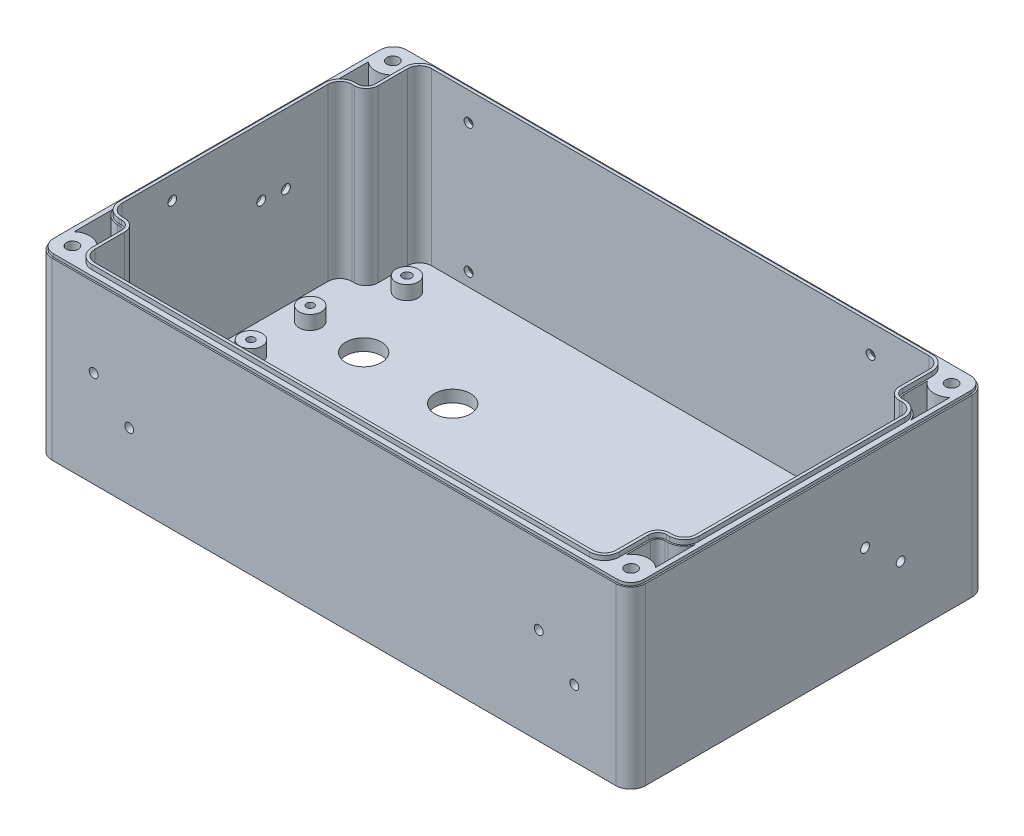
SolidWorks part; units mm, degrees
ref_plane "Front Plane" through (0, 0, 0) normal (0, 0, 1) x (1, 0, 0)
ref_plane "Top Plane" through (0, 0, 0) normal (0, 1, 0) x (1, 0, 0)
ref_plane "Right Plane" through (0, 0, 0) normal (1, 0, 0) x (0, 0, -1)
sketch "Sketch1" plane through (0, 0, 0) normal (0, 1, 0) x (1, 0, 0)
  line L1 (-100, 60) -> (100, 60)
  line L2 (-100, 60) -> (-100, -60)
  line L3 (-100, -60) -> (100, -60)
  line L4 (100, 60) -> (100, -60)
  line L5 (-100, 60) -> (100, -60) construction
  line L6 (-100, -60) -> (100, 60) construction
  point P0 (0, 0)
  dimension "D1" = 200
  dimension "D2" = 120
extrude "Boss-Extrude1" add sketch "Sketch1" along normal blind 60
fillet "Fillet1" radius 5 4 edges at (-100, 30, -60) (100, 30, -60) (100, 30, 60) (-100, 30, 60)
sketch "Sketch2" plane through (0, 60, 0) normal (0, 1, 0) x (1, 0, 0)
  line L0 (0, 60) -> (0, -60) construction
  line L1 (96.7, 56.7) -> (-96.7, 56.7)
  line L2 (96.7, 56.7) -> (96.7, -56.7)
  line L3 (96.7, -56.7) -> (-96.7, -56.7)
  line L4 (-96.7, 56.7) -> (-96.7, -56.7)
  line L5 (96.7, 56.7) -> (-96.7, -56.7) construction
  line L6 (96.7, -56.7) -> (-96.7, 56.7) construction
  line L7 (95, 60) -> (-95, 60) construction
  line L8 (-95, -60) -> (95, -60) construction
  line L9 (-100, 0) -> (99.9439, 0) construction
  line L10 (-100, 55) -> (-100, -55) construction
  line L12 (87.85, -56.7) -> (-87.85, -56.7)
  line L13 (87.85, -56.7) -> (87.85, 56.7)
  line L14 (87.85, 56.7) -> (-87.85, 56.7)
  line L15 (-87.85, -56.7) -> (-87.85, 56.7)
  line L16 (87.85, -56.7) -> (-87.85, 56.7) construction
  line L17 (87.85, 56.7) -> (-87.85, -56.7) construction
  line L18 (96.7, -38.7) -> (-96.7, -38.7)
  line L19 (96.7, -38.7) -> (96.7, 38.7)
  line L20 (96.7, 38.7) -> (-96.7, 38.7)
  line L21 (-96.7, -38.7) -> (-96.7, 38.7)
  line L22 (96.7, -38.7) -> (-96.7, 38.7) construction
  line L23 (96.7, 38.7) -> (-96.7, -38.7) construction
  circle A0 centre (-94.15, 54) radius 2
  circle A2 centre (94.15, 54) radius 2
  circle A3 centre (94.15, -54) radius 2
  circle A4 centre (-94.15, -54) radius 2
  point P0 (0, 0)
  point P18 (0, 0)
  point P19 (0, 0)
  dimension "D5" = 4
  dimension "D1" = 193.4
  dimension "D2" = 113.4
  dimension "D3" = 188.3
  dimension "D4" = 108
  dimension "D6" = 175.7
  dimension "D7" = 77.4
extrude "Cut-Extrude1" cut sketch "Sketch2" against normal offset from surface (56 mm away) 4 contours L20 L13 L1 L15 | L13 L20 L15 L18 | L13 L18 L15 L3 | L15 L20 L4 L18 | L2 L20 L13 L18 | A0 | A4 | A2 | A3 region at (0, 60, -47.7) region at (92.275, 60, 0) region at (0, 60, 0) region at (-92.275, 60, 0) region at (0, 60, 47.7) up to face at (0, 0, 0)
fillet "Fillet2" radius 4 12 edges at (87.85, 32, -56.7) (87.85, 32, -38.7) (96.7, 32, -38.7) (96.7, 32, 38.7) (87.85, 32, 38.7) (87.85, 32, 56.7) (-87.85, 32, 56.7) (-87.85, 32, 38.7) (-96.7, 32, 38.7) (-96.7, 32, -38.7) (-87.85, 32, -56.7) (-87.85, 32, -38.7)
sketch "Sketch3" plane through (0, 60, 0) normal (0, 1, 0) x (1, 0, 0)
  line L1 (83.85, 57.7) -> (-83.85, 57.7)
  line L2 (-88.85, 52.7) -> (-88.85, 42.7)
  line L3 (-91.85, 39.7) -> (-92.7, 39.7)
  line L4 (-97.7, 34.7) -> (-97.7, -34.7)
  line L5 (-92.7, -39.7) -> (-91.85, -39.7)
  line L6 (-88.85, -42.7) -> (-88.85, -52.7)
  line L7 (-83.85, -57.7) -> (83.85, -57.7)
  line L8 (88.85, -52.7) -> (88.85, -42.7)
  line L9 (91.85, -39.7) -> (92.7, -39.7)
  line L10 (97.7, -34.7) -> (97.7, 34.7)
  line L11 (92.7, 39.7) -> (91.85, 39.7)
  line L12 (88.85, 42.7) -> (88.85, 52.7)
  line L13 (87.85, 42.7) -> (87.85, 52.7)
  line L14 (92.7, 38.7) -> (91.85, 38.7)
  line L15 (96.7, -34.7) -> (96.7, 34.7)
  line L16 (91.85, -38.7) -> (92.7, -38.7)
  line L17 (87.85, -52.7) -> (87.85, -42.7)
  line L18 (-83.85, -56.7) -> (83.85, -56.7)
  line L19 (-87.85, -42.7) -> (-87.85, -52.7)
  line L20 (-92.7, -38.7) -> (-91.85, -38.7)
  line L21 (-96.7, 34.7) -> (-96.7, -34.7)
  line L22 (-91.85, 38.7) -> (-92.7, 38.7)
  line L23 (-87.85, 52.7) -> (-87.85, 42.7)
  line L24 (83.85, 56.7) -> (-83.85, 56.7)
  line L25 (87.85, 42.7) -> (87.85, 52.7)
  line L26 (92.7, 38.7) -> (91.85, 38.7)
  line L27 (96.7, -34.7) -> (96.7, 34.7)
  line L28 (91.85, -38.7) -> (92.7, -38.7)
  line L29 (87.85, -52.7) -> (87.85, -42.7)
  line L30 (-83.85, -56.7) -> (83.85, -56.7)
  line L31 (-87.85, -42.7) -> (-87.85, -52.7)
  line L32 (-92.7, -38.7) -> (-91.85, -38.7)
  line L33 (-96.7, 34.7) -> (-96.7, -34.7)
  line L34 (-91.85, 38.7) -> (-92.7, 38.7)
  line L35 (-87.85, 52.7) -> (-87.85, 42.7)
  line L36 (83.85, 56.7) -> (-83.85, 56.7)
  arc A0 (-83.85, 57.7) -> (-88.85, 52.7) centre (-83.85, 52.7) ccw
  arc A1 (-91.85, 39.7) -> (-88.85, 42.7) centre (-91.85, 42.7) ccw
  arc A2 (-92.7, 39.7) -> (-97.7, 34.7) centre (-92.7, 34.7) ccw
  arc A3 (-97.7, -34.7) -> (-92.7, -39.7) centre (-92.7, -34.7) ccw
  arc A4 (-88.85, -42.7) -> (-91.85, -39.7) centre (-91.85, -42.7) ccw
  arc A5 (-88.85, -52.7) -> (-83.85, -57.7) centre (-83.85, -52.7) ccw
  arc A6 (83.85, -57.7) -> (88.85, -52.7) centre (83.85, -52.7) ccw
  arc A7 (91.85, -39.7) -> (88.85, -42.7) centre (91.85, -42.7) ccw
  arc A8 (92.7, -39.7) -> (97.7, -34.7) centre (92.7, -34.7) ccw
  arc A9 (97.7, 34.7) -> (92.7, 39.7) centre (92.7, 34.7) ccw
  arc A10 (88.85, 42.7) -> (91.85, 39.7) centre (91.85, 42.7) ccw
  arc A11 (88.85, 52.7) -> (83.85, 57.7) centre (83.85, 52.7) ccw
  arc A12 (87.85, 42.7) -> (91.85, 38.7) centre (91.85, 42.7) ccw
  arc A13 (96.7, 34.7) -> (92.7, 38.7) centre (92.7, 34.7) ccw
  arc A14 (92.7, -38.7) -> (96.7, -34.7) centre (92.7, -34.7) ccw
  arc A15 (91.85, -38.7) -> (87.85, -42.7) centre (91.85, -42.7) ccw
  arc A16 (83.85, -56.7) -> (87.85, -52.7) centre (83.85, -52.7) ccw
  arc A17 (-87.85, -52.7) -> (-83.85, -56.7) centre (-83.85, -52.7) ccw
  arc A18 (-87.85, -42.7) -> (-91.85, -38.7) centre (-91.85, -42.7) ccw
  arc A19 (-96.7, -34.7) -> (-92.7, -38.7) centre (-92.7, -34.7) ccw
  arc A20 (-92.7, 38.7) -> (-96.7, 34.7) centre (-92.7, 34.7) ccw
  arc A21 (-91.85, 38.7) -> (-87.85, 42.7) centre (-91.85, 42.7) ccw
  arc A22 (-83.85, 56.7) -> (-87.85, 52.7) centre (-83.85, 52.7) ccw
  arc A23 (87.85, 52.7) -> (83.85, 56.7) centre (83.85, 52.7) ccw
  arc A24 (87.85, 42.7) -> (91.85, 38.7) centre (91.85, 42.7) ccw
  arc A25 (96.7, 34.7) -> (92.7, 38.7) centre (92.7, 34.7) ccw
  arc A26 (92.7, -38.7) -> (96.7, -34.7) centre (92.7, -34.7) ccw
  arc A27 (91.85, -38.7) -> (87.85, -42.7) centre (91.85, -42.7) ccw
  arc A28 (83.85, -56.7) -> (87.85, -52.7) centre (83.85, -52.7) ccw
  arc A29 (-87.85, -52.7) -> (-83.85, -56.7) centre (-83.85, -52.7) ccw
  arc A30 (-87.85, -42.7) -> (-91.85, -38.7) centre (-91.85, -42.7) ccw
  arc A31 (-96.7, -34.7) -> (-92.7, -38.7) centre (-92.7, -34.7) ccw
  arc A32 (-92.7, 38.7) -> (-96.7, 34.7) centre (-92.7, 34.7) ccw
  arc A33 (-91.85, 38.7) -> (-87.85, 42.7) centre (-91.85, 42.7) ccw
  arc A34 (-83.85, 56.7) -> (-87.85, 52.7) centre (-83.85, 52.7) ccw
  arc A35 (87.85, 52.7) -> (83.85, 56.7) centre (83.85, 52.7) ccw
  dimension "D1" = 0
  dimension "D2" = 1
extrude "Boss-Extrude2" add sketch "Sketch3" along normal blind 1.55
sketch "Sketch4" plane through (0, 4, 0) normal (0, 1, 0) x (1, 0, 0)
  circle A1 centre (-94.15, 54) radius 2
  circle A2 centre (-94.15, 54) radius 2
  circle A3 centre (94.15, 54) radius 2
  circle A4 centre (94.15, 54) radius 2
  circle A5 centre (-94.15, -54) radius 2
  circle A6 centre (-94.15, -54) radius 2
  circle A7 centre (94.15, -54) radius 2
  circle A8 centre (94.15, -54) radius 2
  dimension "D1" = 0
  dimension "D2" = 0
  dimension "D3" = 0
  dimension "D4" = 0
extrude "Cut-Extrude2" cut sketch "Sketch4" against normal up to next
sketch "Sketch5" plane through (0, 0, 0) normal (0, -1, 0) x (1, 0, 0)
  circle A0 centre (-94.15, 54) radius 3.45
  circle A1 centre (94.15, 54) radius 3.45
  circle A2 centre (94.15, -54) radius 3.45
  circle A3 centre (-94.15, -54) radius 3.45
  dimension "D1" = 6.9
extrude "Cut-Extrude3" cut sketch "Sketch5" against normal blind 52
sketch "Sketch6" plane through (0, 60, 0) normal (0, 1, 0) x (1, 0, 0)
  line L8 (95, 58) -> (-95, 58)
  line L9 (-98, 55) -> (-98, -55)
  line L10 (-95, -58) -> (95, -58)
  line L11 (98, -55) -> (98, 55)
  line L12 (95, 58) -> (-95, 58)
  line L13 (-98, 55) -> (-98, -55)
  line L14 (-95, -58) -> (95, -58)
  line L15 (98, -55) -> (98, 55)
  line L25 (-100, 55) -> (-100, -55) construction
  line L37 (83.85, 58.2) -> (-83.85, 58.2)
  line L38 (89.35, 42.7) -> (89.35, 52.7)
  line L39 (92.7, 40.2) -> (91.85, 40.2)
  line L40 (98.2, -34.7) -> (98.2, 34.7)
  line L41 (91.85, -40.2) -> (92.7, -40.2)
  line L42 (89.35, -52.7) -> (89.35, -42.7)
  line L43 (-83.85, -58.2) -> (83.85, -58.2)
  line L44 (-89.35, -42.7) -> (-89.35, -52.7)
  line L45 (-92.7, -40.2) -> (-91.85, -40.2)
  line L46 (-98.2, 34.7) -> (-98.2, -34.7)
  line L47 (-91.85, 40.2) -> (-92.7, 40.2)
  line L48 (-89.35, 52.7) -> (-89.35, 42.7)
  line L49 (83.85, 58.2) -> (-83.85, 58.2)
  line L50 (89.35, 42.7) -> (89.35, 52.7)
  line L51 (92.7, 40.2) -> (91.85, 40.2)
  line L52 (98.2, -34.7) -> (98.2, 34.7)
  line L53 (91.85, -40.2) -> (92.7, -40.2)
  line L54 (89.35, -52.7) -> (89.35, -42.7)
  line L55 (-83.85, -58.2) -> (83.85, -58.2)
  line L56 (-89.35, -42.7) -> (-89.35, -52.7)
  line L57 (-92.7, -40.2) -> (-91.85, -40.2)
  line L58 (-98.2, 34.7) -> (-98.2, -34.7)
  line L59 (-91.85, 40.2) -> (-92.7, 40.2)
  line L60 (-89.35, 52.7) -> (-89.35, 42.7)
  arc A8 (-95, 58) -> (-98, 55) centre (-95, 55) ccw
  arc A9 (-98, -55) -> (-95, -58) centre (-95, -55) ccw
  arc A10 (95, -58) -> (98, -55) centre (95, -55) ccw
  arc A11 (98, 55) -> (95, 58) centre (95, 55) ccw
  arc A12 (-95, 58) -> (-98, 55) centre (-95, 55) ccw
  arc A13 (-98, -55) -> (-95, -58) centre (-95, -55) ccw
  arc A14 (95, -58) -> (98, -55) centre (95, -55) ccw
  arc A15 (98, 55) -> (95, 58) centre (95, 55) ccw
  circle A24 centre (-94.15, 54) radius 5.85
  circle A25 centre (94.15, 54) radius 5.85
  circle A26 centre (94.15, -54) radius 5.85
  circle A27 centre (-94.15, -54) radius 5.85
  arc A36 (89.35, 52.7) -> (83.85, 58.2) centre (83.85, 52.7) ccw
  arc A37 (89.35, 42.7) -> (91.85, 40.2) centre (91.85, 42.7) ccw
  arc A38 (98.2, 34.7) -> (92.7, 40.2) centre (92.7, 34.7) ccw
  arc A39 (92.7, -40.2) -> (98.2, -34.7) centre (92.7, -34.7) ccw
  arc A40 (91.85, -40.2) -> (89.35, -42.7) centre (91.85, -42.7) ccw
  arc A41 (83.85, -58.2) -> (89.35, -52.7) centre (83.85, -52.7) ccw
  arc A42 (-89.35, -52.7) -> (-83.85, -58.2) centre (-83.85, -52.7) ccw
  arc A43 (-89.35, -42.7) -> (-91.85, -40.2) centre (-91.85, -42.7) ccw
  arc A44 (-98.2, -34.7) -> (-92.7, -40.2) centre (-92.7, -34.7) ccw
  arc A45 (-92.7, 40.2) -> (-98.2, 34.7) centre (-92.7, 34.7) ccw
  arc A46 (-91.85, 40.2) -> (-89.35, 42.7) centre (-91.85, 42.7) ccw
  arc A47 (-83.85, 58.2) -> (-89.35, 52.7) centre (-83.85, 52.7) ccw
  arc A48 (89.35, 52.7) -> (83.85, 58.2) centre (83.85, 52.7) ccw
  arc A49 (89.35, 42.7) -> (91.85, 40.2) centre (91.85, 42.7) ccw
  arc A50 (98.2, 34.7) -> (92.7, 40.2) centre (92.7, 34.7) ccw
  arc A51 (92.7, -40.2) -> (98.2, -34.7) centre (92.7, -34.7) ccw
  arc A52 (91.85, -40.2) -> (89.35, -42.7) centre (91.85, -42.7) ccw
  arc A53 (83.85, -58.2) -> (89.35, -52.7) centre (83.85, -52.7) ccw
  arc A54 (-89.35, -52.7) -> (-83.85, -58.2) centre (-83.85, -52.7) ccw
  arc A55 (-89.35, -42.7) -> (-91.85, -40.2) centre (-91.85, -42.7) ccw
  arc A56 (-98.2, -34.7) -> (-92.7, -40.2) centre (-92.7, -34.7) ccw
  arc A57 (-92.7, 40.2) -> (-98.2, 34.7) centre (-92.7, 34.7) ccw
  arc A58 (-91.85, 40.2) -> (-89.35, 42.7) centre (-91.85, 42.7) ccw
  arc A59 (-83.85, 58.2) -> (-89.35, 52.7) centre (-83.85, 52.7) ccw
  dimension "D1" = 2
  dimension "D2" = 0.5
extrude "Cut-Extrude4" cut sketch "Sketch6" against normal up to surface (56 mm away) contours L59 A58 L60 A24 L13 A57 | A50 L15 A25 L50 A49 L51 | L53 A52 L54 A26 L15 A51 | A56 L13 A27 L56 A55 L57 region at (93.8916, 60, -44.1874) region at (93.8916, 60, 44.1874) region at (-93.8916, 60, -44.1874) region at (-93.8916, 60, 44.1874) up to face at (0, 4, 0)
sketch "Sketch7" plane through (0, 0, 0) normal (0, -1, 0) x (1, 0, 0)
  line L0 (-94.15, 54) -> (-94.15, -54) construction
  line L1 (94.15, -45) -> (-94.15, -45)
  line L2 (94.15, -45) -> (94.15, 45)
  line L3 (94.15, 45) -> (-94.15, 45)
  line L4 (-94.15, -45) -> (-94.15, 45)
  line L5 (94.15, -45) -> (-94.15, 45) construction
  line L6 (94.15, 45) -> (-94.15, -45) construction
  circle A0 centre (-94.15, 45) radius 2.225
  circle A1 centre (94.15, 45) radius 2.225
  circle A2 centre (94.15, -45) radius 2.225
  circle A3 centre (-94.15, -45) radius 2.225
  point P0 (0, 0)
  dimension "D2" = 4.45
  dimension "D1" = 90
extrude "Cut-Extrude5" cut sketch "Sketch7" against normal up to next contours A0 | A1 | A2 | A3
sketch "Sketch8" plane through (0, 4, 0) normal (0, 1, 0) x (1, 0, 0)
  line L0 (0, 60) -> (0, -60) construction
  line L1 (95, 60) -> (-95, 60) construction
  line L2 (-95, -60) -> (95, -60) construction
  line L3 (-100, 0) -> (100, 0) construction
  line L4 (-100, 55) -> (-100, -55) construction
  line L5 (100, -55) -> (100, 55) construction
  line L6 (-80.4, 45) -> (80.4, 45) construction
  line L7 (-80.4, 45) -> (-80.4, -45) construction
  line L8 (-88, 60) -> (-88, -60) construction
  circle A0 centre (-80.4, 45) radius 3.75
  circle A1 centre (-80.4, 45) radius 1.5
  circle A2 centre (80.4, 45) radius 3.75
  circle A3 centre (80.4, 45) radius 1.5
  circle A4 centre (80.4, -45) radius 3.75
  circle A5 centre (80.4, -45) radius 1.5
  circle A6 centre (-80.4, -45) radius 3.75
  circle A7 centre (-80.4, -45) radius 1.5
  circle A8 centre (-57.9, 45) radius 3.75
  circle A9 centre (-57.9, 45) radius 1.25
  circle A12 centre (-57.9, -45) radius 1.25
  circle A13 centre (-57.9, -45) radius 3.75
  circle A16 centre (-88, 0) radius 3.75
  circle A17 centre (-88, 0) radius 1.25
  circle A18 centre (-88, 20) radius 3.75
  circle A19 centre (-88, 20) radius 1.25
  circle A20 centre (-88, -20) radius 1.25
  circle A21 centre (-88, -20) radius 3.75
  circle A22 centre (88, -20) radius 3.75
  circle A23 centre (88, -20) radius 1.25
  circle A24 centre (88, 0) radius 1.25
  circle A25 centre (88, 0) radius 3.75
  circle A26 centre (88, 20) radius 3.75
  circle A27 centre (88, 20) radius 1.25
  dimension "D1" = 7.5
  dimension "D2" = 3
  dimension "D5" = 2.5
  dimension "D3" = 160.8
  dimension "D4" = 90
  dimension "D6" = 22.5
  dimension "D7" = 176
  dimension "D8" = 40
extrude "Boss-Extrude3" add sketch "Sketch8" along normal blind 4.7
sketch "Sketch9" plane through (0, 60, 0) normal (0, 1, 0) x (1, 0, 0)
  line L0 (95, 59.5) -> (-95, 59.5)
  line L1 (-99.5, 55) -> (-99.5, -55)
  line L2 (-95, -59.5) -> (95, -59.5)
  line L3 (99.5, -55) -> (99.5, 55)
  line L4 (95, 60) -> (-95, 60)
  line L5 (-100, 55) -> (-100, -55)
  line L6 (-95, -60) -> (95, -60)
  line L7 (100, -55) -> (100, 55)
  line L8 (95, 60) -> (-95, 60)
  line L9 (-100, 55) -> (-100, -55)
  line L10 (-95, -60) -> (95, -60)
  line L11 (100, -55) -> (100, 55)
  arc A0 (-95, 59.5) -> (-99.5, 55) centre (-95, 55) ccw
  arc A1 (-99.5, -55) -> (-95, -59.5) centre (-95, -55) ccw
  arc A2 (95, -59.5) -> (99.5, -55) centre (95, -55) ccw
  arc A3 (99.5, 55) -> (95, 59.5) centre (95, 55) ccw
  arc A4 (-95, 60) -> (-100, 55) centre (-95, 55) ccw
  arc A5 (-100, -55) -> (-95, -60) centre (-95, -55) ccw
  arc A6 (95, -60) -> (100, -55) centre (95, -55) ccw
  arc A7 (100, 55) -> (95, 60) centre (95, 55) ccw
  arc A8 (-95, 60) -> (-100, 55) centre (-95, 55) ccw
  arc A9 (-100, -55) -> (-95, -60) centre (-95, -55) ccw
  arc A10 (95, -60) -> (100, -55) centre (95, -55) ccw
  arc A11 (100, 55) -> (95, 60) centre (95, 55) ccw
  dimension "D1" = 0
  dimension "D2" = 0.5
extrude "Cut-Extrude6" cut sketch "Sketch9" against normal blind 1
sketch "Sketch10" plane through (0, 8.7, 0) normal (0, 1, 0) x (1, 0, 0)
  circle A1 centre (-57.9, 45) radius 3.75
  circle A2 centre (-57.9, 45) radius 3.75
  dimension "D1" = 0
extrude "Cut-Extrude7" cut sketch "Sketch10" against normal up to surface (4.7 mm away) up to face at (88, 4, -23.75)
sketch "Sketch11" plane through (0, 0, -60) normal (0, 0, -1) x (-1, 0, 0)
  circle A1 centre (71.35, 52) radius 1.5 construction
  circle A2 centre (71.35, 52) radius 1.5
  circle A3 centre (-64.15, 52) radius 1.5 construction
  circle A4 centre (-64.15, 52) radius 1.5
  circle A5 centre (-64.15, 8.5) radius 1.5 construction
  circle A6 centre (-64.15, 8.5) radius 1.5
  circle A7 centre (71.35, 8.5) radius 1.5 construction
  circle A8 centre (71.35, 8.5) radius 1.5
extrude "Cut-Extrude8" cut sketch "Sketch11" against normal up to next
hole_wizard "CSK for M3 Flat Head Machine Screw1" positions "Sketch12" profile "Sketch14" countersink size "M3" standard "ANSI Metric"
sketch "Sketch12" plane through (0, 0, -60) normal (0, 0, -1) x (-1, 0, 0)
  point P0 (71.35, 52)
  point P3 (71.35, 8.5)
  point P6 (-64.15, 8.5)
  point P9 (-64.15, 52)
sketch "Sketch14" plane through (-71.35, 52, -60) normal (1, 0, 0) x (0, 1, 0)
  line L0 (0, 0) -> (0, 4.2003)
  line L1 (0, 4.2003) -> (1.5, 3.299)
  line L2 (1.5, 3.299) -> (1.5, 1.8)
  line L3 (1.5, 1.8) -> (3, 0.3)
  line L4 (3, 0.3) -> (3, 0)
  line L6 (3, 0) -> (0, 0)
  line L7 (-1.5, 1.8) -> (-3, 0.3) construction
  line L10 (0, 4.2003) -> (-1.5, 3.299) construction
  line L11 (0, -6.35) -> (0, 107.95) construction
  dimension "Hole Dia." = 3
  dimension "Hole Depth" = 3.299
  dimension "C'Sink Dia." = 6
  dimension "C'Sink Angle" = 90
  dimension "Drill Angle" = 118
  dimension "Head Clearance" = 0.3
sketch "Sketch15" plane through (-100, 0, 0) normal (-1, 0, 0) x (0, 0, 1)
  circle A0 centre (17.8, 53.8172) radius 1.5 construction
  circle A1 centre (17.8, 53.8172) radius 1.5
  circle A2 centre (-12.2, 38.8172) radius 1.5 construction
  circle A3 centre (-12.2, 38.8172) radius 1.5
  circle A4 centre (20.5, 17.0172) radius 1.8 construction
  circle A5 centre (20.5, 17.0172) radius 1.8
  circle A6 centre (-20.5, 38.0172) radius 1.8 construction
  circle A7 centre (-20.5, 38.0172) radius 1.8
  circle A8 centre (-20.5, 38.0172) radius 1.5
  circle A9 centre (20.5, 17.0172) radius 1.5
extrude "Cut-Extrude9" cut sketch "Sketch15" against normal up to next contours A8 | A3 | A1 | A9 region at (-100, 53.8172, 17.8) region at (-100, 38.8172, -12.2) region at (-100, 38.0172, -20.5) region at (-100, 17.0172, 20.5)
hole_wizard "CSK for M3 Flat Head Machine Screw2" positions "Sketch16" profile "Sketch18" countersink size "M3" standard "ANSI Metric"
sketch "Sketch16" plane through (-100, 0, 0) normal (-1, 0, 0) x (0, 0, 1)
  point P0 (-20.5, 38.0172)
  point P3 (-12.2, 38.8172)
  point P6 (17.8, 53.8172)
  point P9 (20.5, 17.0172)
sketch "Sketch18" plane through (-100, 38.0172, -20.5) normal (0, 1, 0) x (0, 0, 1)
  line L0 (0, 0) -> (0, 4.2003)
  line L1 (0, 4.2003) -> (1.5, 3.299)
  line L2 (1.5, 3.299) -> (1.5, 1.8)
  line L3 (1.5, 1.8) -> (3, 0.3)
  line L4 (3, 0.3) -> (3, 0)
  line L6 (3, 0) -> (0, 0)
  line L7 (-1.5, 1.8) -> (-3, 0.3) construction
  line L10 (0, 4.2003) -> (-1.5, 3.299) construction
  line L11 (0, -6.35) -> (0, 107.95) construction
  dimension "Hole Dia." = 3
  dimension "Hole Depth" = 3.299
  dimension "C'Sink Dia." = 6
  dimension "C'Sink Angle" = 90
  dimension "Drill Angle" = 118
  dimension "Head Clearance" = 0.3
sketch "Sketch20" plane through (0, 0, 60) normal (0, 0, 1) x (1, 0, 0)
  line L0 (-95, 0) -> (95, 0) construction
  line L1 (-100, 0) -> (-100, 59) construction
  line L2 (0, 81.508) -> (0, -38.0481) construction
  line L3 (-81, 32.45) -> (-100, 32.45) construction
  line L4 (81, 22.45) -> (100, 22.45) construction
  line L5 (100, 59) -> (100, 0) construction
  line L6 (-81, 32.45) -> (-69, 22.45) construction
  line L7 (69, 32.45) -> (81, 22.45) construction
  circle A0 centre (-81, 32.45) radius 1.5
  circle A1 centre (-69, 22.45) radius 1.5
  circle A2 centre (69, 32.45) radius 1.5
  circle A3 centre (81, 22.45) radius 1.5
  dimension "D1" = 3
  dimension "D2" = 32.45
  dimension "D3" = 19
  dimension "D4" = 12
  dimension "D5" = 10
extrude "Cut-Extrude10" cut sketch "Sketch20" against normal up to next
sketch "Sketch21" plane through (100, 0, 0) normal (1, 0, 0) x (0, 0, -1)
  line L1 (-50, 22.45) -> (55, 22.45) construction
  line L2 (-50, 23.95) -> (-50, 20.95)
  line L3 (-50, 23.95) -> (-50, 20.95)
  line L4 (55, 0) -> (55, 59) construction
  line L5 (60, 59) -> (60, 0) construction
  circle A0 centre (31, 22.45) radius 1.5
  circle A1 centre (19, 32.45) radius 1.5
  point P12 (0, 0)
  dimension "D2" = 3
  dimension "D3" = 29
  dimension "D4" = 12
  dimension "D5" = 10
  dimension "D1" = 10
extrude "Cut-Extrude11" cut sketch "Sketch21" against normal up to next contours A1 | A0
sketch "Sketch23" plane through (0, 0, 0) normal (0, -1, 0) x (1, 0, 0)
  line L0 (-100, 0) -> (100, 0) construction
  line L1 (-100, -55) -> (-100, 55) construction
  line L2 (100, 55) -> (100, -55) construction
  line L3 (-100, -20) -> (100, -20) construction
  line L4 (70, -15.9) -> (70, -24.1) construction
  line L5 (62.125, -15.9) -> (77.875, -15.9)
  line L6 (62.125, -15.9) -> (62.125, -24.1)
  line L7 (62.125, -24.1) -> (77.875, -24.1)
  line L8 (77.875, -15.9) -> (77.875, -24.1)
  line L9 (62.125, -15.9) -> (77.875, -24.1) construction
  line L10 (62.125, -24.1) -> (77.875, -15.9) construction
  circle A0 centre (-70, -20) radius 6
  circle A1 centre (-40, -20) radius 6
  circle A2 centre (74.875, -18.9) radius 3
  circle A3 centre (74.875, -21.1) radius 3
  circle A4 centre (59.75, -20) radius 1.35
  circle A5 centre (80.25, -20) radius 1.35
  point P12 (70, -20)
  point P19 (77.875, -18.9)
  dimension "D2" = 12
  dimension "D8" = 6
  dimension "D10" = 2.7
  dimension "D1" = 20
  dimension "D3" = 30
  dimension "D4" = 30
  dimension "D5" = 30
  dimension "D6" = 8.2
  dimension "D7" = 15.75
  dimension "D9" = 20.5
extrude "Cut-Extrude12" cut sketch "Sketch23" against normal up to next contours L7 A3 A2 L5 L6 | A2 A3 L8 | A0 | A1 | A2 A3 | A3 A2 | A3 A2 | A4 | A5 region at (67.264, 0, -20) region at (74.875, 0, -17.5886) region at (77.8127, 0, -20) region at (74.875, 0, -20) region at (74.875, 0, -22.4114) region at (-70, 0, -20) region at (-40, 0, -20) region at (59.75, 0, -20) region at (80.25, 0, -20)
fillet "Fillet3" radius 1 2 edges at (62.125, 2, -15.9) (62.125, 2, -24.1)
hole_wizard "CSK for M2.5 Flat Head Machine Screw1" positions "Sketch24" profile "Sketch26" countersink size "M2.5" standard "ANSI Metric" end condition up to next
sketch "Sketch24" plane through (0, 0, 0) normal (0, -1, 0) x (-1, 0, 0)
  point P0 (-59.75, 20)
  point P3 (-80.25, 20)
sketch "Sketch26" plane through (59.75, 0, -20) normal (1, 0, 0) x (0, 0, -1)
  line L0 (0, 0) -> (0, 61.55)
  line L1 (0, 61.55) -> (1.25, 61.55)
  line L2 (1.25, 61.55) -> (1.25, 1.45)
  line L3 (1.25, 1.45) -> (2.5, 0.2)
  line L4 (2.5, 0.2) -> (2.5, 0)
  line L6 (2.5, 0) -> (0, 0)
  line L7 (-1.25, 1.45) -> (-2.5, 0.2) construction
  line L11 (0, -6.35) -> (0, 107.95) construction
  dimension "Thru Hole Dia." = 2.5
  dimension "Thru Hole Depth" = 61.55
  dimension "C'Sink Dia." = 5
  dimension "C'Sink Angle" = 90
  dimension "Head Clearance" = 0.2
